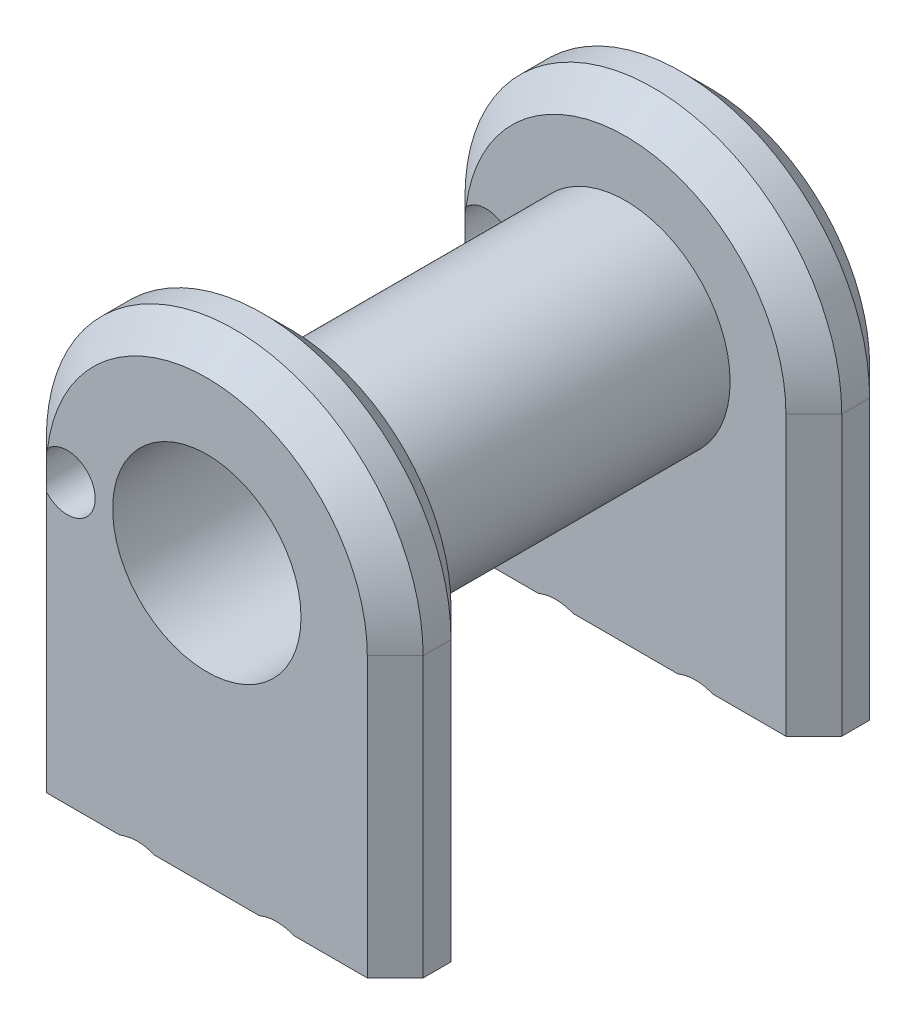
SolidWorks part; units mm, degrees
ref_plane "Front Plane" through (0, 0, 0) normal (0, 0, 1) x (1, 0, 0)
ref_plane "Top Plane" through (0, 0, 0) normal (0, 1, 0) x (1, 0, 0)
ref_plane "Right Plane" through (0, 0, 0) normal (1, 0, 0) x (0, 0, -1)
sketch "Sketch1" plane through (0, 0, 0) normal (0, 0, 1) x (1, 0, 0)
  line L0 (-13.5, 0) -> (-13.5, -20)
  line L1 (-13.5, -20) -> (13.5, -20)
  line L2 (13.5, -20) -> (13.5, 0)
  arc A0 (13.5, 0) -> (-13.5, 0) centre (0, 0) ccw
  dimension "D1" = 27
  dimension "D2" = 20
extrude "Boss-Extrude1" add sketch "Sketch1" along normal blind 6
sketch "Sketch2" plane through (0, 0, 6) normal (0, 0, 1) x (1, 0, 0)
  circle A0 centre (0, 0) radius 7.5
  dimension "D1" = 15
extrude "Boss-Extrude2" add sketch "Sketch2" along normal blind 24
sketch "Sketch3" plane through (0, 0, 30) normal (0, 0, 1) x (1, 0, 0)
  line L3 (-13.5, 0) -> (-13.5, -20)
  line L4 (-13.5, -20) -> (13.5, -20)
  line L5 (13.5, -20) -> (13.5, 0)
  line L6 (-13.5, 0) -> (-13.5, -20)
  line L7 (-13.5, -20) -> (13.5, -20)
  line L8 (13.5, -20) -> (13.5, 0)
  arc A2 (13.5, 0) -> (-13.5, 0) centre (0, 0) ccw
  arc A3 (13.5, 0) -> (-13.5, 0) centre (0, 0) ccw
  dimension "D1" = 0
extrude "Boss-Extrude3" add sketch "Sketch3" along normal blind 6
sketch "Sketch4" plane through (0, 0, 36) normal (0, 0, 1) x (1, 0, 0)
  circle A0 centre (0, 0) radius 6.75
  dimension "D1" = 13.5
extrude "Cut-Extrude1" cut sketch "Sketch4" against normal through all
sketch "Sketch5" plane through (0, -20, 0) normal (0, -1, 0) x (1, 0, 0)
  line L0 (-5, 33) -> (-13.5, 33) construction
  line L1 (-5, 33) -> (5, 33) construction
  line L2 (-5, 33) -> (-5, 3) construction
  line L3 (-5, 3) -> (5, 3) construction
  line L4 (5, 33) -> (5, 3) construction
  line L5 (-13.5, 36) -> (-13.5, 30) construction
  line L6 (-5, 3) -> (-13.5, 3) construction
  line L7 (-13.5, 6) -> (-13.5, 0) construction
  line L8 (0, 3) -> (0, 0) construction
  circle A0 centre (-5, 33) radius 2.25
  circle A1 centre (5, 33) radius 2.25
  circle A2 centre (-5, 3) radius 2.25
  circle A3 centre (5, 3) radius 2.25
  dimension "D3" = 4.5
  dimension "D1" = 10
  dimension "D2" = 30
extrude "Cut-Extrude2" cut sketch "Sketch5" against normal blind 13
chamfer "Chamfer1" distance 1 angle 45 4 edges at (-2.75, -20, 3) (7.25, -20, 3) (7.25, -20, 33) (-2.75, -20, 33)
chamfer "Chamfer2" distance 2 angle 45 12 edges at (13.5, -10, 0) (-13.5, -10, 0) (0, 13.5, 0) (13.5, -10, 36) (-13.5, -10, 36) (0, 13.5, 36) (13.5, -10, 6) (-13.5, -10, 6) (0, 13.5, 6) (13.5, -10, 30) (-13.5, -10, 30) (0, 13.5, 30)
sketch "Sketch6" plane through (0, 0, 36) normal (0, 0, 1) x (1, 0, 0)
  line L0 (0, 0) -> (-10, 0) construction
  circle A0 centre (-10, 0) radius 2
  dimension "D1" = 4
  dimension "D2" = 10
extrude "Cut-Extrude3" cut sketch "Sketch6" against normal through all
